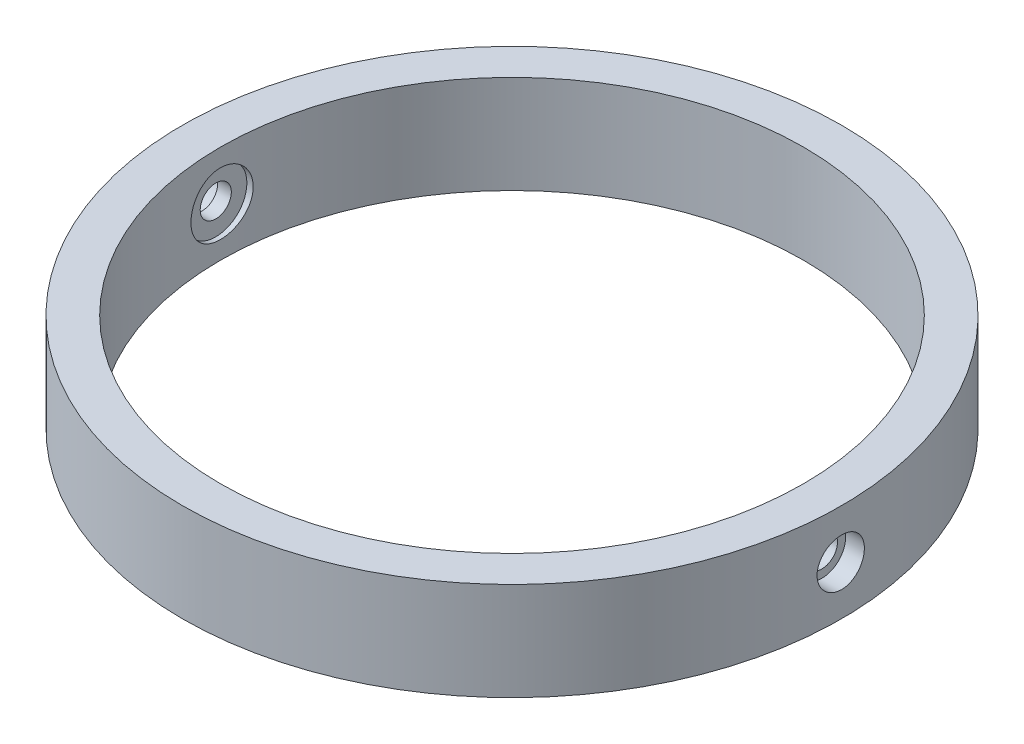
SolidWorks part; units mm, degrees
ref_plane "Front Plane" through (0, 0, 0) normal (0, 0, 1) x (1, 0, 0)
ref_plane "Top Plane" through (0, 0, 0) normal (0, 1, 0) x (1, 0, 0)
ref_plane "Right Plane" through (0, 0, 0) normal (1, 0, 0) x (0, 0, -1)
sketch "Sketch1" plane through (0, 0, 0) normal (0, 1, 0) x (1, 0, 0)
  circle A0 centre (0, 0) radius 59.5
  circle A1 centre (0, 0) radius 67.25
  dimension "D1" = 119
  dimension "D2" = 134.5
extrude "Boss-Extrude1" add sketch "Sketch1" along normal blind 20
ref_plane "Plane1" through (0, 0, 67.3) normal (0, 0, 1) x (1, 0, 0)
ref_plane "Plane2" through (67.25, 0, 0) normal (1, 0, 0) x (0, 0, -1)
sketch "Sketch3" plane through (67.25, 0, 0) normal (1, 0, 0) x (0, 0, -1)
sketch "Sketch4" plane through (67.25, 0, 0) normal (1, 0, 0) x (0, 0, -1)
  line L0 (67.25, 20) -> (-67.25, 20) construction
  circle A0 centre (0, 10) radius 3.175
  dimension "D1" = 6.35
  dimension "D2" = 10
extrude "Cut-Extrude2" cut sketch "Sketch4" against normal blind 200
sketch "Sketch5" plane through (67.25, 0, 0) normal (1, 0, 0) x (0, 0, -1)
  circle A0 centre (0, 10) radius 4.826
  dimension "D1" = 9.652
extrude "Cut-Extrude3" cut sketch "Sketch5" against normal blind 4
mirror "Mirror1" about plane through (0, 0, 0) normal (1, 0, 0) of "Cut-Extrude3"
ref_plane "Plane3" through (59.45, 0, 0) normal (1, 0, 0) x (0, 0, -1)
sketch "Sketch6" plane through (59.45, 0, 0) normal (1, 0, 0) x (0, 0, -1)
  circle A0 centre (0, 10) radius 6.35
  circle A1 centre (0, 10) radius 3.175 construction
  dimension "D1" = 12.7
extrude "Cut-Extrude4" cut sketch "Sketch6" against normal blind 1 and the other way blind 1
mirror "Mirror2" about plane through (0, 0, 0) normal (1, 0, 0) of "Cut-Extrude4"
ref_axis "Axis2" through (0, 21, 0) along (0, -1, 0)
ref_plane "Servo Reference Plane" through (0, 0, 0) normal (-0.7071, 0, 0.7071) x (0, -1, 0)
